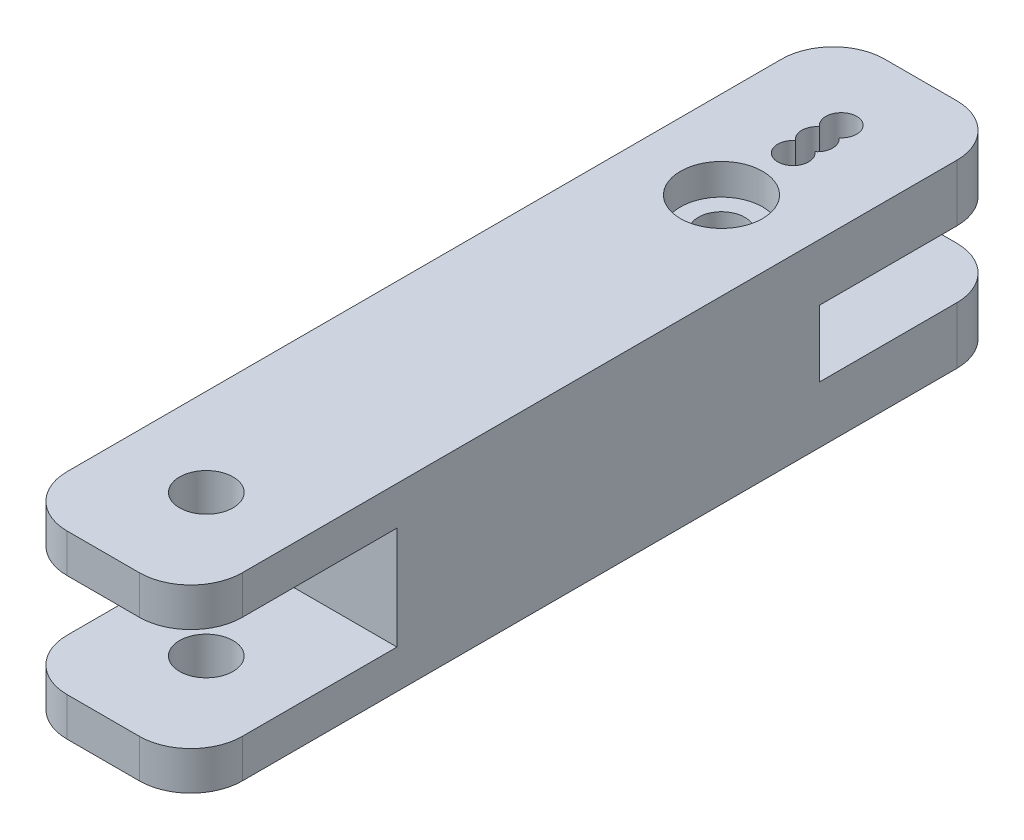
SolidWorks part; units mm, degrees
ref_plane "Front Plane" through (0, 0, 0) normal (0, 0, 1) x (1, 0, 0)
ref_plane "Top Plane" through (0, 0, 0) normal (0, 1, 0) x (1, 0, 0)
ref_plane "Right Plane" through (0, 0, 0) normal (1, 0, 0) x (0, 0, -1)
sketch "Sketch1" plane through (0, 0, 0) normal (0, 1, 0) x (1, 0, 0)
  line L6 (8.5, 10) -> (8.5, 60) construction
  line L7 (0, 0) -> (17, 0)
  line L8 (0, 0) -> (0, 79.3333)
  line L9 (0, 79.3333) -> (17, 79.3333)
  line L10 (17, 0) -> (17, 79.3333)
  circle A1 centre (8.5, 10) radius 2.6
  arc A2 (7.5142, 70.4999) -> (7.5142, 68.1665) centre (8.457, 69.3332) ccw
  arc A3 (7.5142, 68.1665) -> (9.3998, 68.1665) centre (8.457, 66.9999) ccw
  circle A5 centre (8.5, 60) radius 3.985
  arc A6 (9.3998, 70.4999) -> (7.5142, 70.4999) centre (8.457, 71.6665) ccw
  arc A7 (9.3998, 68.1665) -> (9.3998, 70.4999) centre (8.457, 69.3332) ccw
  point P2 (0, 0)
  point P8 (8.5, 0)
  dimension "D4" = 17
  dimension "D2" = 10
  dimension "D3" = 5.2
  dimension "D5" = 50
  dimension "D10" = 7.97
  dimension "D9" = 2.3333
  dimension "D11" = 1.5
  dimension "D1" = 79.3333
  dimension "D7" = 9.3333
  dimension "D8" = 7
extrude "Boss-Extrude1" add sketch "Sketch1" along normal blind 17.5
fillet "Fillet1" radius 5 4 edges at (0, 8.75, 0) (17, 8.75, 0) (17, 8.75, -79.3333) (0, 8.75, -79.3333)
ref_plane "Plane1" through (0, 8.75, 0) normal (0, 1, 0) x (1, 0, 0)
sketch "Sketch3" plane through (0, 8.75, 0) normal (0, 1, 0) x (1, 0, 0)
  circle A0 centre (8.5, 60) radius 2.25
  circle A1 centre (8.5, 60) radius 3.985
  dimension "D1" = 7.97
  dimension "D2" = 4.5
extrude "Boss-Extrude2" add sketch "Sketch3" along normal offset from surface 3 and the other way offset from surface 3 up to face at (8.5, 17.5, -7.4) other way up to face at (8.457, 0, -69.3332)
ref_axis "Axis1" through (8.457, 34.5399, -66.9999) along (0, -1, 0)
sketch "Sketch2" plane through (17, 0, 0) normal (1, 0, 0) x (0, 0, -1)
  line L0 (0, 0) -> (0, 17.5) construction
  line L1 (-20, 13.75) -> (20, 13.75)
  line L2 (-20, 13.75) -> (-20, 3.75)
  line L3 (-20, 3.75) -> (20, 3.75)
  line L4 (20, 13.75) -> (20, 3.75)
  line L5 (-20, 13.75) -> (20, 3.75) construction
  line L6 (-20, 3.75) -> (20, 13.75) construction
  line L7 (79.3333, 17.5) -> (79.3333, 0) construction
  line L13 (60.9999, 11.975) -> (97.6667, 11.975)
  line L14 (60.9999, 11.975) -> (60.9999, 5.525)
  line L15 (60.9999, 5.525) -> (97.6667, 5.525)
  line L16 (97.6667, 11.975) -> (97.6667, 5.525)
  line L17 (60.9999, 11.975) -> (97.6667, 5.525) construction
  line L18 (60.9999, 5.525) -> (97.6667, 11.975) construction
  line L19 (66.9999, 34.5399) -> (66.9999, 0) construction
  point P0 (0, 8.75)
  point P7 (79.3333, 8.75)
  point P8 (79.3333, 8.75)
  dimension "D1" = 10
  dimension "D2" = 40
  dimension "D3" = 6
  dimension "D4" = 6.45
extrude "Cut-Extrude2" cut sketch "Sketch2" against normal through all
